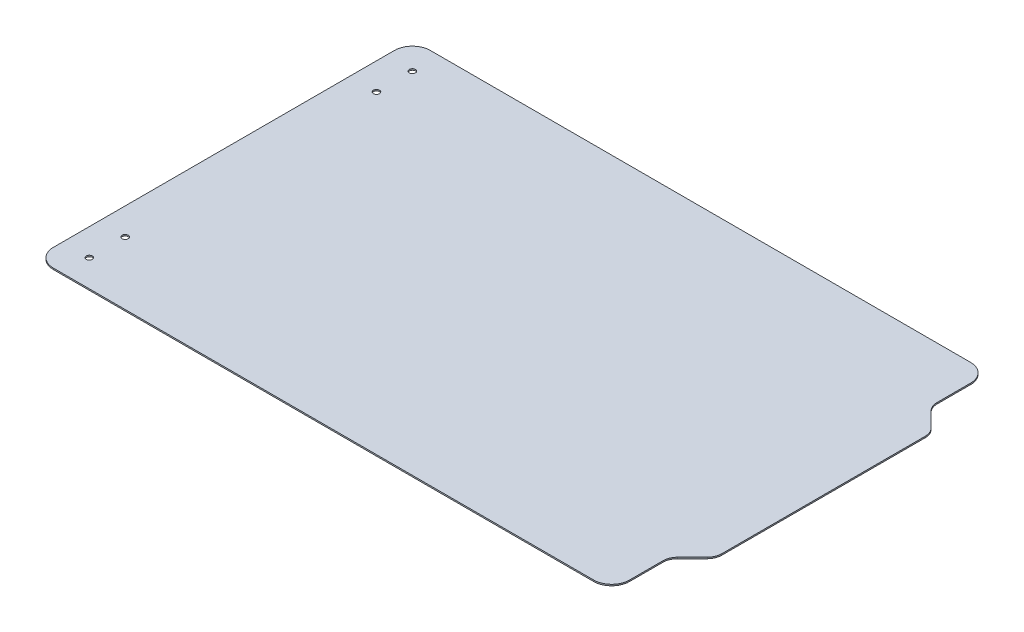
SolidWorks part; units mm, degrees
material "AISI 1020 Steel, Cold Rolled"
ref_plane "Front Plane" through (0, 0, 0) normal (0, 0, 1) x (1, 0, 0)
ref_plane "Top Plane" through (0, 0, 0) normal (0, 1, 0) x (1, 0, 0)
ref_plane "Right Plane" through (0, 0, 0) normal (1, 0, 0) x (0, 0, -1)
sketch "Sketch1" plane through (0, 0, 0) normal (0, 1, 0) x (1, 0, 0)
  line L1 (-167, 105) -> (167, 105)
  line L2 (-167, 105) -> (-167, -105)
  line L3 (-167, -105) -> (167, -105)
  line L4 (167, 105) -> (167, -105)
  line L5 (-167, 105) -> (167, -105) construction
  line L6 (-167, -105) -> (167, 105) construction
  point P0 (0, 0)
  dimension "D1" = 334
  dimension "D2" = 210
extrude "Boss-Extrude1" add sketch "Sketch1" along normal blind 0.76
sketch "Sketch2" plane through (0, 0, 0) normal (0, -1, 0) x (-1, 0, 0)
  line L0 (-167, -60) -> (-154, -73)
  line L5 (-167, -105) -> (-167, 105) construction
  line L6 (-154, -73) -> (-154, -105)
  line L7 (167, -105) -> (-167, -105) construction
  line L8 (-154, -105) -> (-167, -105)
  line L9 (-167, -105) -> (-167, -60)
  line L10 (-0.418, 0) -> (0.418, 0) construction
  line L11 (-154, 105) -> (-167, 105)
  line L12 (-154, 73) -> (-154, 105)
  line L13 (-167, 60) -> (-154, 73)
  line L14 (-167, 105) -> (-167, 60)
  dimension "D1" = 13
  dimension "D2" = 45
  dimension "D3" = 32
extrude "Cut-Extrude1" cut sketch "Sketch2" against normal blind 0.76
fillet "Fillet1" radius 8 4 edges at (154, 0.38, -73) (167, 0.38, -60) (154, 0.38, 73) (167, 0.38, 60)
fillet "Fillet2" radius 10 4 edges at (154, 0.38, -105) (-167, 0.38, -105) (-167, 0.38, 105) (154, 0.38, 105)
sketch "Sketch3" plane through (0, 0, 0) normal (0, -1, 0) x (1, 0, 0)
  circle A0 centre (-152, -70) radius 1.7 construction
  circle A1 centre (-152, -90) radius 1.7 construction
  circle A2 centre (-152, 70) radius 1.7 construction
  circle A3 centre (-152, 90) radius 1.7 construction
  circle A4 centre (-152, -70) radius 1.7
  circle A5 centre (-152, -90) radius 1.7
  circle A6 centre (-152, 70) radius 1.7
  circle A7 centre (-152, 90) radius 1.7
extrude "Cut-Extrude2" cut sketch "Sketch3" against normal through all
